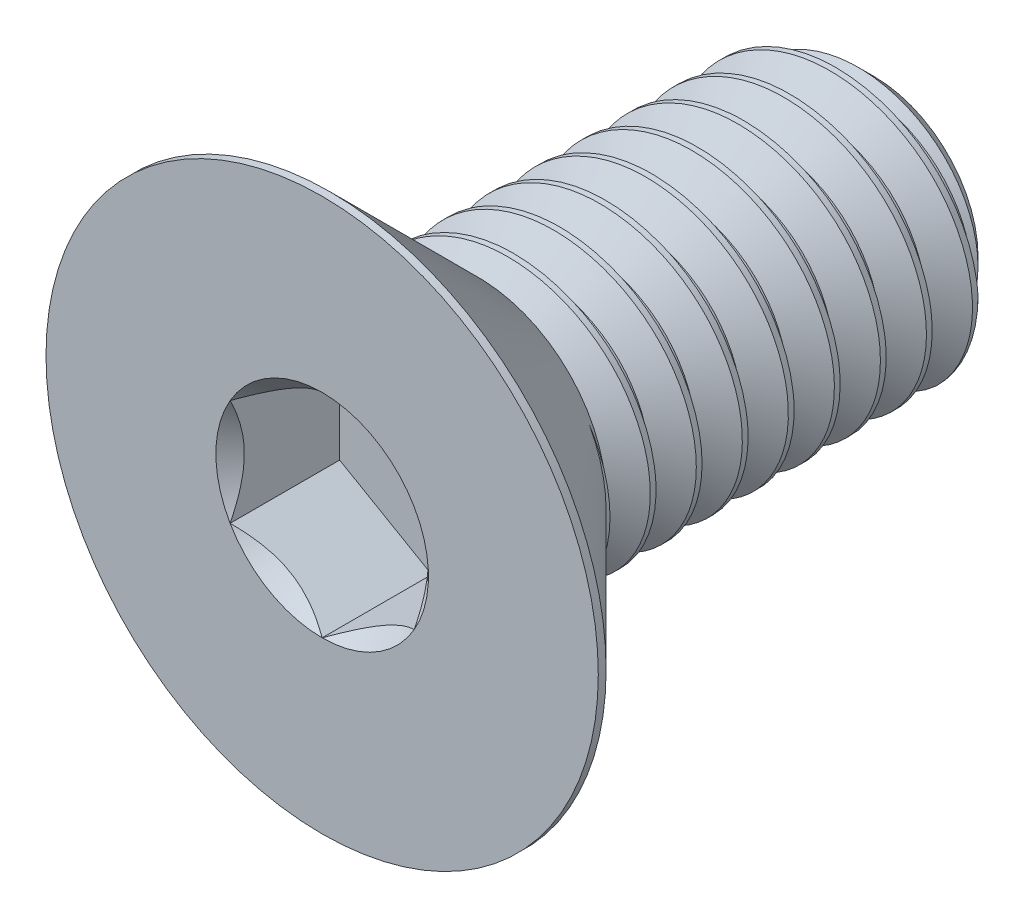
SolidWorks part; units mm, degrees
ref_plane "Front" through (0, 0, 0) normal (0, 0, 1) x (1, 0, 0)
ref_plane "Top" through (0, 0, 0) normal (0, 1, 0) x (1, 0, 0)
ref_plane "Right" through (0, 0, 0) normal (1, 0, 0) x (0, 0, -1)
sketch "Sketch11" plane through (0, 0, 0) normal (1, 0, 0) x (0, 0, -1)
  line L0 (-3, 3) -> (3, 3) construction
  line L5 (-3, 3) -> (-3, -3) construction
  line L6 (3, 1.5) -> (3, -1.5) construction
  line L7 (-2.99, 1) -> (-2.99, -1) construction
  line L8 (2.9688, 1.5541) -> (3.4688, 1.5541) construction
  line L9 (3.4688, 1.5541) -> (3.2188, 1.1211) construction
  line L10 (3.2188, 1.1211) -> (2.9688, 1.5541) construction
  line L11 (3.1875, 1.1752) -> (3.25, 1.1752) construction
  line L12 (3.2188, 1.1752) -> (3.2188, 1.1211) construction
  line L13 (2.9844, 1.5271) -> (3.4531, 1.5271) construction
  line L14 (3.2188, 1.5541) -> (3.2188, 1.5) construction
  line L15 (3, 1.5) -> (3.4375, 1.5) construction
  line L17 (-2.915, 3) -> (0.085, 0) construction
  line L18 (0.085, 0) -> (-2.915, -3) construction
  point P3 (-1.3, 3)
  point P8 (0, 3)
  point P21 (3.2188, 1.5271)
  point P26 (-3, 0)
  point P28 (-2.99, 0)
  point P29 (3, 0)
  dimension "Length" = 6
  dimension "Head Diameter" = 6
  dimension "Thread Major Diameter" = 3
  dimension "Head Height" = 1.7
  dimension "Drive Size" = 2
  dimension "Thread Pitch" = 0.5
  dimension "D1" = 0.0625
  dimension "D2" = 0.01
  dimension "D3" = 0.085
  dimension "Countersink Angle" = 90
sketch "Sketch1" plane through (0, 0, 0) normal (1, 0, 0) x (0, 0, -1)
  line L2 (-1.3, 1.5) -> (3, 1.5)
  line L3 (3, 1.5) -> (3, 0)
  line L4 (-1.81, 1.5) -> (-1.81, 0)
  line L5 (-1.3, 1.5) -> (-1.81, 1.5)
  line L6 (-3, 3) -> (-3, -3) construction
  line L7 (3, 1.5) -> (3, -1.5) construction
  line L8 (-1.81, 0) -> (3, 0)
  dimension "D1" = 1.19
revolve "Revolve1" add sketch "Sketch1" angle 360 mid plane about L8
chamfer "Chamfer1" distance 0.375 angle 45 1 edges at (0, -1.5, -3)
sketch "Sketch7" plane through (0, 0, 0) normal (1, 0, 0) x (0, 0, -1)
  line L2 (-3, 3) -> (-2.915, 3)
  line L5 (-1.3, 1.385) -> (-1.3, 0)
  line L6 (-3, 3) -> (-3, 0)
  line L8 (-3, 3) -> (-3, -3) construction
  line L9 (-3, 0) -> (-1.3, 0)
  line L12 (-2.915, 3) -> (-1.3, 1.385)
  line L13 (-2.915, 3) -> (0.085, 0) construction
revolve "Revolve2" add sketch "Sketch7" angle 360 mid plane about L9 region at (0, 1.1696, 2.2571)
ref_plane "Plane1" through (0, 0, 1.3) normal (0, 0, 1) x (1, 0, 0)
sketch "Sketch5" plane through (0, 0, 3) normal (0, 0, 1) x (1, 0, 0)
  line L1 (1, -0.5774) -> (1, 0.5774)
  line L2 (1, 0.5774) -> (0, 1.1547)
  line L3 (0, 1.1547) -> (-1, 0.5774)
  line L4 (-1, 0.5774) -> (-1, -0.5774)
  line L5 (-1, -0.5774) -> (0, -1.1547)
  line L6 (0, -1.1547) -> (1, -0.5774)
  circle A0 centre (0, 0) radius 1 construction
extrude "Cut-Extrude2" cut sketch "Sketch5" against normal blind 1.19
sketch "Sketch6" plane through (0, 0, 3) normal (0, 0, -1) x (-1, 0, 0)
  circle A0 centre (0, 0) radius 1.1547
extrude "Cut-Extrude3" cut sketch "Sketch6" along normal blind 1.19 draft 45
sketch "Sketch12" plane through (0, 0, -3) normal (0, 0, -1) x (-1, 0, 0)
  circle A0 centre (0, 0) radius 1.5 construction
  circle A1 centre (0, 0) radius 1.5
curve "Helix/Spiral1" pitch 0.5 height 6 radius 1.5 centre (0, 0, -3) axis (0, 0, 1) start towards (0, 1, 0)
sketch "Sketch13" plane through (0, 0, 0) normal (1, 0, 0) x (0, 0, -1)
  line L0 (2.9844, 1.5271) -> (3.4531, 1.5271)
  line L1 (3.4531, 1.5271) -> (3.25, 1.1752)
  line L2 (3.25, 1.1752) -> (3.1875, 1.1752)
  line L3 (3.1875, 1.1752) -> (2.9844, 1.5271)
sweep "Cut-Sweep1" cut profiles "Sketch13" path "Helix/Spiral1" align with end faces yes
combine bodies "Combine1" operation type add bodies to combine 113 127
equation "\"D1@Chamfer1\"=\"Thread Pitch@Sketch11\" * .75"
equation "\"D1@Cut-Extrude2\"= \"Head Height@Sketch11\" * .7"
equation "\"D1@Cut-Extrude3\" = \"D1@Cut-Extrude2\""
equation "\"D1@Sketch11\"=\"Thread Pitch@Sketch11\"/8"
equation "\"D3@Sketch11\"=\"Head Height@Sketch11\"*.05"
equation "\"D4@Helix/Spiral1\"=\"Thread Pitch@Sketch11\""
equation "\"D1@Sketch1\"=\"Head Height@Sketch11\"*.7"
equation "\"D3@Helix/Spiral1\"=\"Length@Sketch11\""
